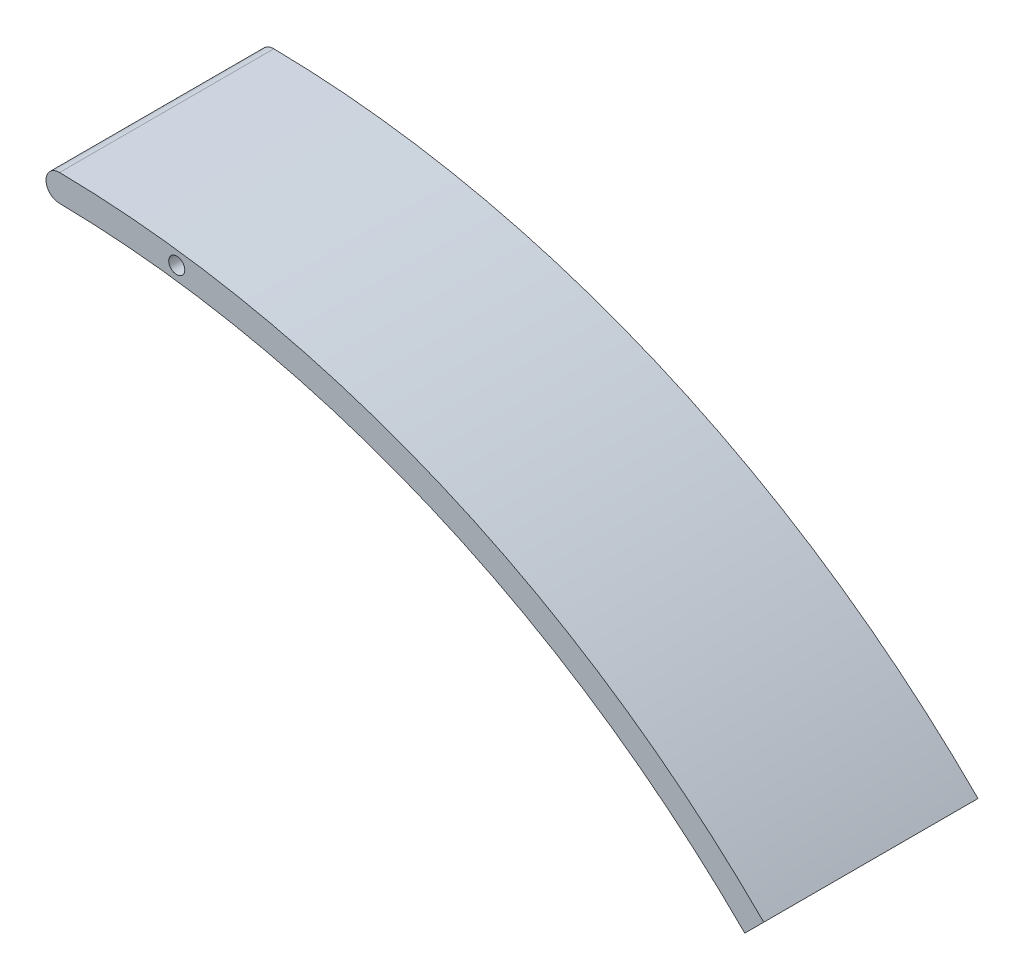
SolidWorks part; units mm, degrees
material "Plastique personnalisé"
ref_plane "Plan de face" through (0, 0, 0) normal (0, 0, 1) x (1, 0, 0)
ref_plane "Plan de dessus" through (0, 0, 0) normal (0, 1, 0) x (1, 0, 0)
ref_plane "Plan de droite" through (0, 0, 0) normal (1, 0, 0) x (0, 0, -1)
sketch "Esquisse1" plane through (0, 0, 0) normal (0, 0, 1) x (1, 0, 0)
  line L0 (0, 379) -> (0, 369)
  line L1 (267.9935, 267.9935) -> (260.9224, 260.9224)
  arc A0 (0, 369) -> (260.9224, 260.9224) centre (0, 0) cw
  arc A1 (0, 379) -> (267.9935, 267.9935) centre (0, 0) cw
  arc A2 (141.2102, 340.9115) -> (48.1642, 365.8432) centre (0, 0) ccw
  circle A3 centre (48.8168, 370.8004) radius 3
  dimension "D6" = 6
  dimension "D1" = 379
  dimension "D2" = 45
  dimension "D3" = 45
  dimension "D4" = 369
  dimension "D5" = 15
extrude "Boss.-Extru.1" add sketch "Esquisse1" along normal blind 80 contours A1 L0 A0 L1 A3 region at (143.9163, 347.4447, 0)
fillet "Congé2" radius 5 2 edges at (0, 369, 40) (0, 379, 40)
sketch "Esquisse2" plane through (0, 0, 0) normal (0.7071, -0.7071, 0) x (0, 0, -1)
  line L0 (-80, 369) -> (0, 369) construction
  line L1 (-60, 369) -> (-20, 369)
  line L2 (-60, 369) -> (-60, 373)
  line L3 (-60, 373) -> (-20, 373)
  line L4 (-20, 369) -> (-20, 373)
  point P9 (-40, 369)
  dimension "D1" = 4
  dimension "D2" = 40
  dimension "D3" = 40
extrude "Enlèv. mat.-Extru.1" cut sketch "Esquisse2" against normal blind 10
